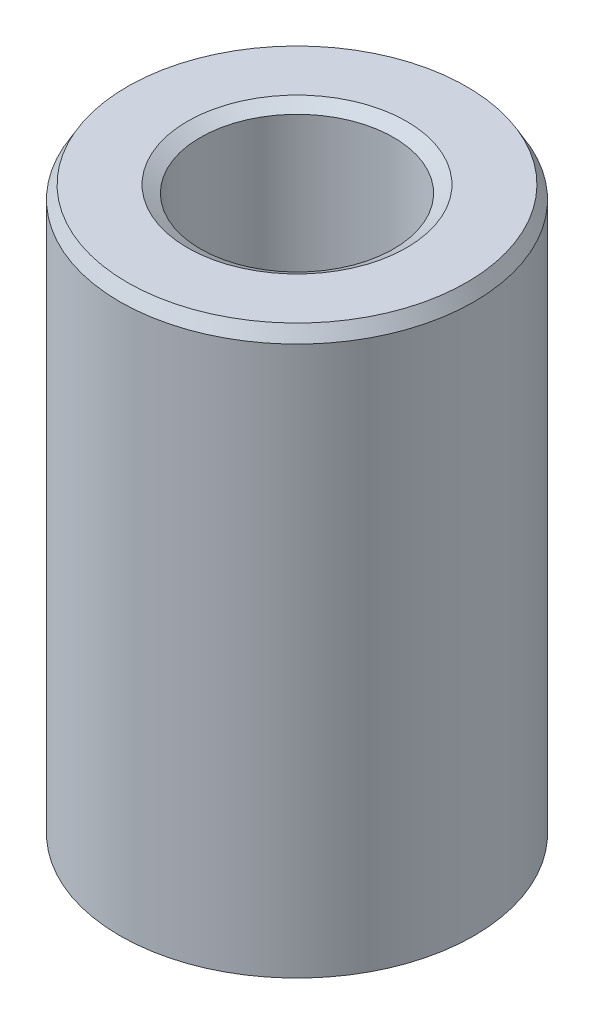
SolidWorks part; units mm, degrees
ref_plane "Front Plane" through (0, 0, 0) normal (0, 0, 1) x (1, 0, 0)
ref_plane "Top Plane" through (0, 0, 0) normal (0, 1, 0) x (1, 0, 0)
ref_plane "Right Plane" through (0, 0, 0) normal (1, 0, 0) x (0, 0, -1)
sketch "Sketch1" plane through (0, 0, 0) normal (0, 1, 0) x (1, 0, 0)
  circle A0 centre (0, 0) radius 5
  dimension "SLEEVE_OD" = 10
extrude "Boss-Extrude1" add sketch "Sketch1" along normal blind 16.0737
sketch "Sketch2" plane through (0, 0, 0) normal (0, 1, 0) x (1, 0, 0)
  circle A0 centre (0, 0) radius 2.7271
  dimension "BORE_D" = 5.4542
extrude "Cut-Extrude1" cut sketch "Sketch2" along normal through all
chamfer "Chamfer1" distance 0.3659 angle 30 4 edges at (0, 16.0737, 2.7271) (0, 0, 2.7271) (0, 0, 5) (0, 16.0737, 5) first distance on face at (0, 16.0737, 2.7271) first distance on face at (0, 0, 2.7271) first distance on face at (0, 16.0737, 5)
